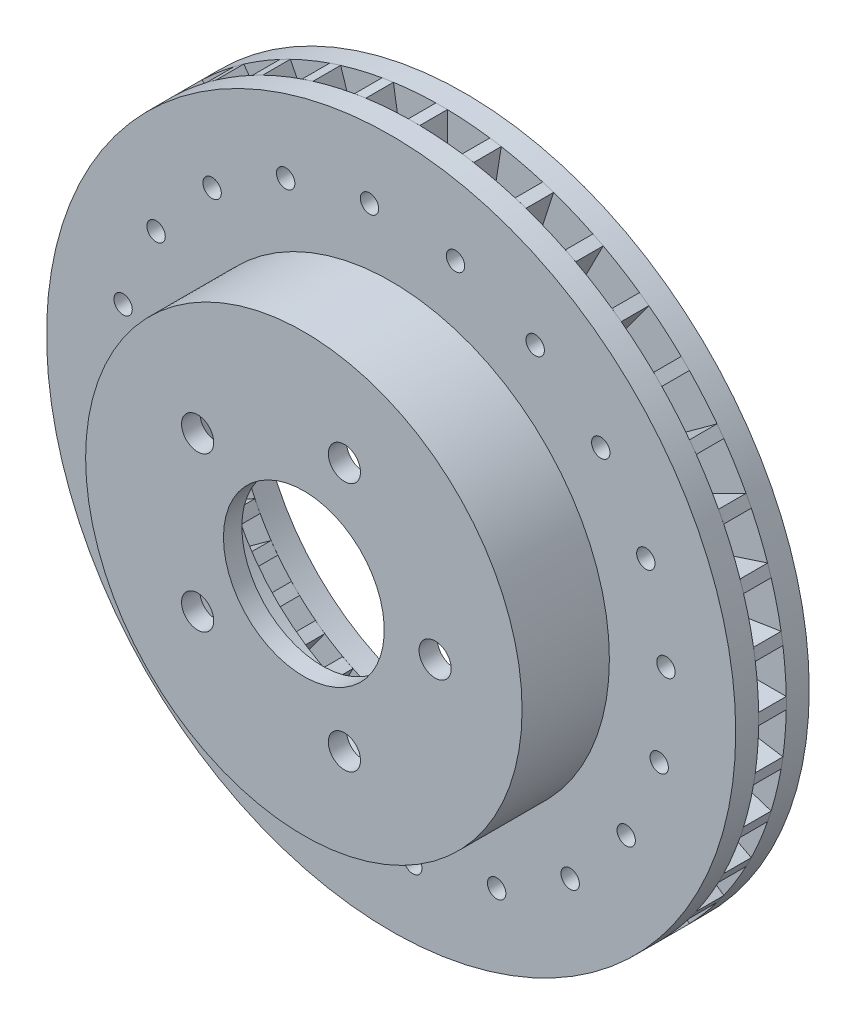
SolidWorks part; units mm, degrees
ref_plane "前视基准面" through (0, 0, 0) normal (0, 0, 1) x (1, 0, 0)
ref_plane "上视基准面" through (0, 0, 0) normal (0, 1, 0) x (1, 0, 0)
ref_plane "右视基准面" through (0, 0, 0) normal (1, 0, 0) x (0, 0, -1)
sketch "草图3" plane through (0, 0, 0) normal (0, 0, 1) x (1, 0, 0)
  circle A0 centre (0, 0) radius 150
  circle A1 centre (0, 0) radius 90
extrude "凸台-拉伸2" add sketch "草图3" along normal blind 10
ref_plane "基准面1" through (0, 0, 10) normal (0, 0, 1) x (1, 0, 0)
sketch "草图4" plane through (0, 0, 10) normal (0, 0, 1) x (1, 0, 0)
  line L0 (90, -2.5) -> (150, -2.5)
  line L1 (150, -2.5) -> (150, 2.5)
  line L2 (150, 2.5) -> (90, 2.5)
  line L3 (90, 2.5) -> (90, -2.5)
extrude "凸台-拉伸3" add sketch "草图4" along normal blind 12
ref_axis "基准轴1" through (0, 0, 73.5) along (0, 0, -1)
pattern_circular "阵列(圆周)1" count 40 over 360 about axis through (0, 0, 73.5) along (0, 0, -1) of "凸台-拉伸3"
ref_plane "基准面2" through (0, 0, 22) normal (0, 0, 1) x (1, 0, 0)
sketch "草图5" plane through (0, 0, 22) normal (0, 0, 1) x (1, 0, 0)
  circle A0 centre (0, 0) radius 150
  circle A1 centre (0, 0) radius 90
extrude "凸台-拉伸4" add sketch "草图5" along normal blind 10
sketch "草图6" plane through (0, 0, 0) normal (0, 1, 0) x (1, 0, 0)
  line L0 (0, 0) -> (0, -100) construction
  line L1 (85, -22) -> (95, -22)
  line L2 (95, -22) -> (95, -70)
  line L3 (95, -70) -> (35, -70)
  line L4 (35, -70) -> (35, -62)
  line L5 (35, -62) -> (85, -62)
  line L6 (85, -62) -> (85, -22)
revolve "旋转2" add sketch "草图6" angle 360 about L0
ref_plane "基准面3" through (0, 0, 70) normal (0, 0, 1) x (1, 0, 0)
sketch "草图7" plane through (0, 0, 70) normal (0, 0, 1) x (1, 0, 0)
  circle A0 centre (57.15, 0) radius 7
  circle A1 centre (17.6603, 54.3529) radius 7
  circle A2 centre (-46.2353, 33.5919) radius 7
  circle A3 centre (-46.2353, -33.5919) radius 7
  circle A4 centre (17.6603, -54.3529) radius 7
extrude "切除-拉伸1" cut sketch "草图7" against normal blind 8
ref_plane "基准面4" through (0, 0, 32) normal (0, 0, 1) x (1, 0, 0)
sketch "草图9" plane through (0, 0, 32) normal (0, 0, 1) x (1, 0, 0)
  circle A0 centre (119.6301, 9.4151) radius 4
  circle A1 centre (110.8655, 45.922) radius 4
  circle A2 centre (91.2487, 77.9338) radius 4
  circle A3 centre (62.6998, 102.3168) radius 4
  circle A4 centre (28.0134, 116.6844) radius 4
  circle A5 centre (-9.4151, 119.6301) radius 4
  circle A6 centre (-45.922, 110.8655) radius 4
  circle A7 centre (-77.9338, 91.2487) radius 4
  circle A8 centre (-102.3168, 62.6998) radius 4
  circle A9 centre (-116.6844, 28.0134) radius 4
  circle A10 centre (-119.6301, -9.4151) radius 4
  circle A11 centre (-110.8655, -45.922) radius 4
  circle A12 centre (-91.2487, -77.9338) radius 4
  circle A13 centre (-62.6998, -102.3168) radius 4
  circle A14 centre (-28.0134, -116.6844) radius 4
  circle A15 centre (9.4151, -119.6301) radius 4
  circle A16 centre (45.922, -110.8655) radius 4
  circle A17 centre (77.9338, -91.2487) radius 4
  circle A18 centre (102.3168, -62.6998) radius 4
  circle A19 centre (116.6844, -28.0134) radius 4
extrude "切除-拉伸4" cut sketch "草图9" against normal through all
